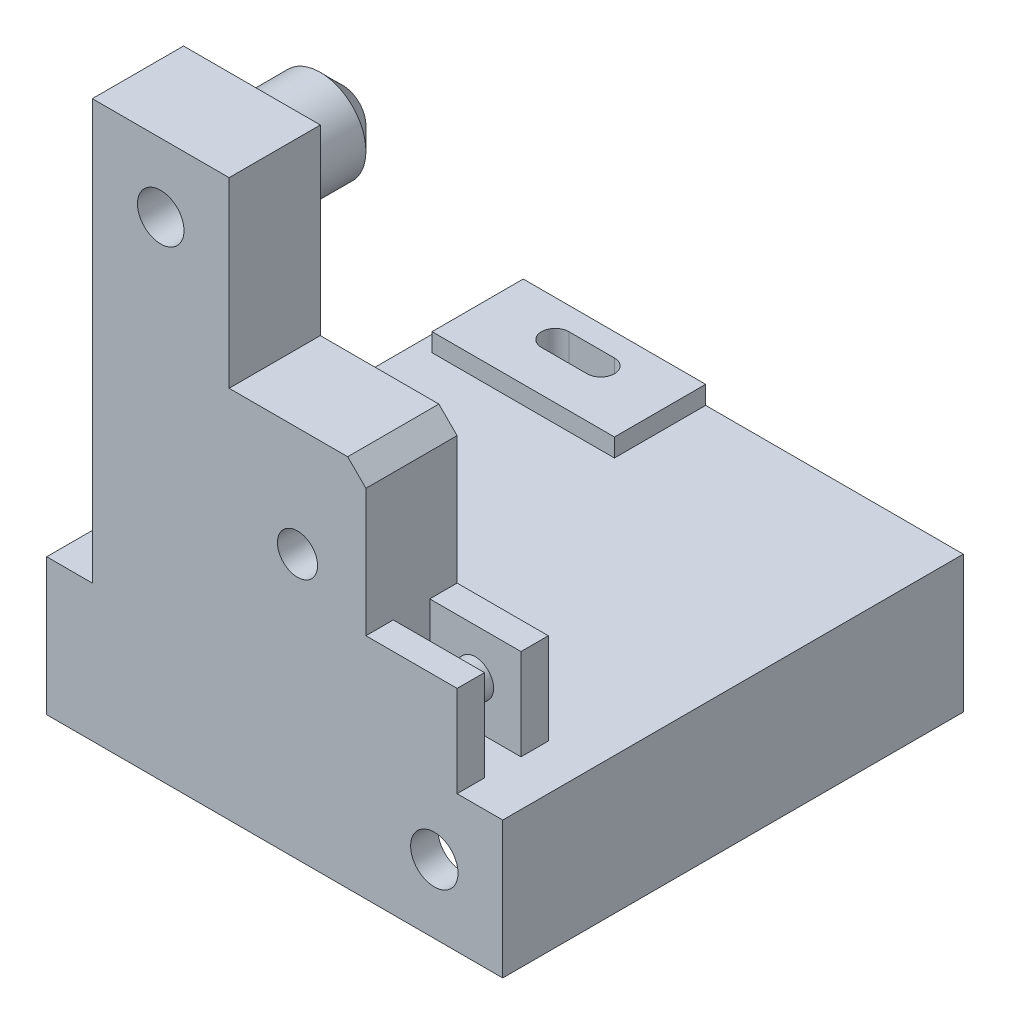
SolidWorks part; units mm, degrees
ref_plane "Front Plane" through (0, 0, 0) normal (0, 0, 1) x (1, 0, 0)
ref_plane "Top Plane" through (0, 0, 0) normal (0, 1, 0) x (1, 0, 0)
ref_plane "Right Plane" through (0, 0, 0) normal (1, 0, 0) x (0, 0, -1)
sketch "Sketch1" plane through (0, 0, 0) normal (0, 0, 1) x (1, 0, 0)
  line L0 (-15, 0) -> (-15, 46)
  line L1 (-15, 46) -> (0, 46)
  line L2 (0, 46) -> (0, 26)
  line L5 (0, 26) -> (15, 26)
  line L6 (15, 26) -> (15, 0)
  line L12 (-15, 0) -> (15, 0)
  circle A0 centre (-7.5, 38.5) radius 2.55
  circle A1 centre (7.5, 14) radius 2.2
  point P8 (0, 0)
  point P12 (-7.5, 46)
  point P16 (7.5, 26)
  dimension "D7" = 5.1
  dimension "D9" = 4.4
  dimension "D1" = 46
  dimension "D2" = 15
  dimension "D3" = 30
  dimension "D6" = 20
  dimension "D8" = 7.5
  dimension "D10" = 12
extrude "Boss-Extrude1" add sketch "Sketch1" along normal blind 6 and the other way blind 4
sketch "Sketch2" plane through (15, 0, 0) normal (1, 0, 0) x (0, 0, -1)
  line L0 (-6, 0) -> (4, 0) construction
  line L1 (-6, 0) -> (-6, 26) construction
  circle A0 centre (-1, 5) radius 2.5
  dimension "D1" = 5
  dimension "D2" = 5
  dimension "D3" = 5
extrude "Boss-Extrude2" [suppressed] add sketch "Sketch2" along normal blind 6
sketch "Sketch3" [suppressed] plane through (21, 0, 0) normal (1, 0, 0) x (0, 0, -1)
  circle A0 centre (-5, 5) radius 4.5
  circle A1 centre (-5, 5) radius 2.5
  circle A2 centre (-5, 5) radius 2.5 construction
  dimension "D1" = 0
  dimension "D2" = 2
extrude "Boss-Extrude3" [suppressed] add sketch "Sketch3" along normal blind 2
ref_plane "Plane1" through (0, 0, -4) normal (0, 0, -1) x (-1, 0, 0)
sketch "Sketch4" plane through (0, 0, -4) normal (0, 0, -1) x (-1, 0, 0)
  line L0 (-15, 0) -> (-15, 10)
  line L1 (-15, 0) -> (-25, 0)
  line L2 (-15, 10) -> (-25, 10)
  line L3 (-25, 0) -> (-25, 10)
  line L4 (-15, 0) -> (-15, 26) construction
  dimension "D1" = 10
  dimension "D2" = 10
extrude "Boss-Extrude4" add sketch "Sketch4" against normal blind 10
sketch "Sketch5" plane through (25, 0, 0) normal (1, 0, 0) x (0, 0, -1)
  line L0 (-3, 10) -> (1, 10)
  line L1 (-3, 10) -> (-3, 0)
  line L2 (1, 10) -> (1, 0)
  line L3 (-3, 0) -> (1, 0)
  line L4 (-6, 10) -> (4, 10) construction
  line L5 (-6, 0) -> (4, 0) construction
  line L7 (-6, 10) -> (4, 10) construction
  point P8 (-1, 10)
  dimension "D1" = 4
extrude "Cut-Extrude1" cut sketch "Sketch5" against normal up to surface (10 mm away) up to face at (15, 18, 1)
sketch "Sketch6" plane through (0, 0, -1) normal (0, 0, 1) x (1, 0, 0)
  line L0 (25, 10) -> (25, 0) construction
  line L1 (15, 10) -> (25, 10) construction
  circle A0 centre (20, 5) radius 2
  dimension "D1" = 4
  dimension "D2" = 5
  dimension "D3" = 5
extrude "Boss-Extrude5" add sketch "Sketch6" along normal up to next
fillet "Fillet1" [suppressed] radius 2
chamfer "Chamfer1" distance 2 angle 45 1 edges at (15, 26, 1)
sketch "Sketch7" plane through (0, 0, 0) normal (0, -1, 0) x (1, 0, 0)
  line L1 (25, 6) -> (-15, 6) construction
  line L2 (25, 6) -> (25, -9.5) construction
  line L3 (25, -9.5) -> (-15, -9.5) construction
  line L4 (-15, 6) -> (-15, -9.5) construction
  line L5 (-15, 6) -> (-15, -4) construction
  line L12 (30, -14.5) -> (-20, -14.5)
  line L24 (-16.5, -4) -> (16.5, -4) construction
  line L32 (30, 11) -> (-20, 11) construction
  line L33 (-20, 11) -> (-20, -14.5) construction
  line L34 (30, 11) -> (30, -14.5) construction
  line L35 (-20, -14.5) -> (-20, 6)
  line L36 (-20, 6) -> (30, 6)
  line L37 (30, 6) -> (30, -14.5)
  line L38 (-15, 6) -> (25, 6) construction
  dimension "D2" = 5.5
  dimension "D1" = 5
extrude "Boss-Extrude6" add sketch "Sketch7" along normal blind 15
sketch "Sketch12" plane through (0, 0, 0) normal (0, 1, 0) x (1, 0, 0)
  line L0 (-15, 4) -> (25, 4) construction
  line L3 (-20, 10) -> (-2.5, 10) construction
  line L4 (-20, -6) -> (-20, 14.5) construction
  line L5 (-10.75, 11.5) -> (-5.75, 11.5)
  line L6 (-10.75, 8.5) -> (-5.75, 8.5)
  circle A2 centre (-8.25, 10) radius 1.5 construction
  arc A3 (-10.75, 11.5) -> (-10.75, 8.5) centre (-10.75, 10) ccw
  arc A4 (-5.75, 11.5) -> (-5.75, 8.5) centre (-5.75, 10) cw
  point P12 (-8.25, 8.5)
  point P13 (-8.25, 11.5)
  point P14 (-11.25, 10)
  dimension "D1" = 3
  dimension "D2" = 3
  dimension "D3" = 17.5
  dimension "D4" = 6
  dimension "D5" = 5
sketch "Sketch13" plane through (0, 0, -14.5) normal (0, 0, -1) x (-1, 0, 0)
  line L1 (-30, 0) -> (20, 0)
  line L2 (-30, 0) -> (-30, -15)
  line L3 (-30, -15) -> (20, -15)
  line L4 (20, 0) -> (20, -15)
  point P6 (0, 0)
  point P7 (0, 0)
  point P8 (-29.3982, -0.3108)
  point P10 (0, 0)
  point P11 (19.1631, -13.7926)
extrude "Boss-Extrude9" add sketch "Sketch13" along normal blind 30
sketch "Sketch14" plane through (0, 0, 0) normal (0, 1, 0) x (1, 0, 0)
  line L0 (-20, 24.25) -> (30, 24.25) construction
  line L3 (30, 44.5) -> (30, -6) construction
  line L4 (-20, -6) -> (-20, 44.5) construction
  line L7 (0, 4) -> (-15, 4) construction
  point P2 (0, 0)
  point P8 (0, 0)
  point P9 (0, 0)
  point P10 (0, 0)
  dimension "D1" = 20.25
ref_plane "Plane2" through (0, 0, -24.25) normal (0, 0, -1) x (-1, 0, 0)
sketch "Sketch16" plane through (0, -15, 0) normal (0, -1, 0) x (1, 0, 0)
  line L8 (27, -41.5) -> (27, 3)
  line L9 (27, -41.5) -> (27, 3)
  line L10 (-17, -41.5) -> (27, -41.5)
  line L11 (27, 3) -> (-17, 3)
  line L14 (-17, -41.5) -> (27, -41.5)
  line L16 (27, 3) -> (-17, 3)
  line L17 (-17, 3) -> (-17, -41.5)
  line L18 (-17, 3) -> (-17, -41.5)
  dimension "D1" = 3
extrude "Cut-Extrude3" cut sketch "Sketch16" against normal blind 12
sketch "Sketch17" plane through (0, 0, 6) normal (0, 0, 1) x (1, 0, 0)
  line L1 (-20, 0) -> (30, 0) construction
  line L2 (30, -15) -> (30, 0) construction
  circle A0 centre (22.5, -7.5) radius 2.6
  point P2 (0, 0)
  dimension "D1" = 5.2
  dimension "D2" = 7.5
  dimension "D3" = 7.5
extrude "Cut-Extrude4" cut sketch "Sketch17" against normal up to next
sketch "Sketch18" plane through (-20, 0, 0) normal (-1, 0, 0) x (0, 0, 1)
  line L1 (-14, -15) -> (-16, -15)
  line L2 (-14, -15) -> (-14, 0)
  line L3 (-14, 0) -> (-16, 0)
  line L4 (-16, -15) -> (-16, 0)
  line L6 (-44.5, -15) -> (-44.5, 0) construction
  line L7 (6, 0) -> (-44.5, 0) construction
  line L8 (6, -15) -> (-44.5, -15) construction
  point P4 (0, 0)
  point P10 (0, 0)
  point P11 (0, 0)
  dimension "D1" = 2
  dimension "D2" = 28.5
extrude "Boss-Extrude11" add sketch "Sketch18" along normal blind 5
fillet "Fillet2" radius 5 1 edges at (-20, -7.5, -16)
ref_plane "Plane3" through (-7.5, 0, 0) normal (1, 0, 0) x (0, 0, -1)
sketch "Sketch19" plane through (-7.5, 0, 0) normal (-1, 0, 0) x (0, 0, 1)
  line L0 (-4, 38.5) -> (-14, 38.5)
  line L1 (-4, 46) -> (-4, 0) construction
  line L2 (-11.5, 43.5) -> (-4, 43.5)
  line L3 (-4, 43.5) -> (-4, 38.5)
  line L4 (-4, 46) -> (6, 46) construction
  line L5 (-14, 38.5) -> (-14, 41)
  line L6 (-11.5, 43.5) -> (-14, 41)
  dimension "D2" = 135
  dimension "D1" = 7.5
  dimension "D3" = 10
  dimension "D4" = 5
  dimension "D5" = 2.5
revolve "Revolve1" add sketch "Sketch19" angle 360 about L0
sketch "Sketch20" plane through (0, 0, -4) normal (0, 0, 1) x (1, 0, 0)
  circle A1 centre (-7.5, 38.5) radius 2.55
  circle A2 centre (-7.5, 38.5) radius 2.55
  dimension "D1" = 0
extrude "Cut-Extrude5" cut sketch "Sketch20" against normal up to next
fillet "Fillet5" radius 1.5 1 edges at (-12.5, 38.5, -4)
extrude "Cut-Extrude6" cut sketch "Sketch12" against normal blind 3 contours A4 L6 A3 L5
sketch "Sketch22" plane through (0, 0, 0) normal (0, 1, 0) x (1, 0, 0)
  line L0 (22, 4) -> (-22, 4) construction
  line L1 (-18.25, 14) -> (1.75, 14)
  line L2 (-18.25, 14) -> (-18.25, 4)
  line L3 (-18.25, 4) -> (1.75, 4)
  line L4 (1.75, 14) -> (1.75, 4)
  line L5 (-8.25, 4) -> (-8.25, 14) construction
  line L6 (-10.75, 8.5) -> (-5.75, 8.5) construction
  line L7 (-10.75, 11.5) -> (-5.75, 11.5) construction
  line L8 (-10.75, 8.5) -> (-5.75, 8.5)
  line L9 (-10.75, 11.5) -> (-5.75, 11.5)
  arc A2 (-5.75, 8.5) -> (-5.75, 11.5) centre (-5.75, 10) ccw construction
  arc A3 (-10.75, 11.5) -> (-10.75, 8.5) centre (-10.75, 10) ccw construction
  arc A4 (-5.75, 8.5) -> (-5.75, 11.5) centre (-5.75, 10) ccw
  arc A5 (-10.75, 11.5) -> (-10.75, 8.5) centre (-10.75, 10) ccw
  point P15 (-8.25, 11.5)
  dimension "D1" = 20
  dimension "D2" = 10
extrude "Boss-Extrude12" add sketch "Sketch22" along normal blind 2
mirror "Mirror2" [suppressed] about plane through (0, 0, -24.25) normal (0, 0, -1)
pattern_linear "LPattern1" count 2 spacing 30.5 along (0, 0, -1) of "Boss-Extrude12", "Cut-Extrude6"
